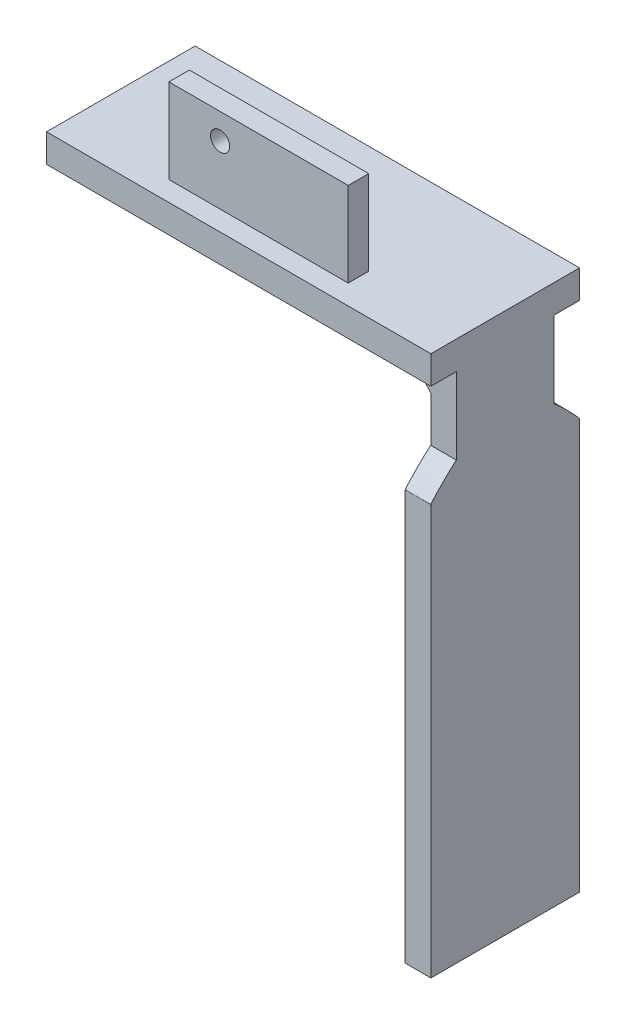
SolidWorks part; units mm, degrees
ref_plane "Front Plane" through (0, 0, 0) normal (0, 0, 1) x (1, 0, 0)
ref_plane "Top Plane" through (0, 0, 0) normal (0, 1, 0) x (1, 0, 0)
ref_plane "Right Plane" through (0, 0, 0) normal (1, 0, 0) x (0, 0, -1)
sketch "Sketch1" plane through (0, 0, 0) normal (0, 1, 0) x (1, 0, 0)
  line L1 (0, 0) -> (60, 0)
  line L2 (0, 0) -> (0, -23.2)
  line L3 (0, -23.2) -> (60, -23.2)
  line L4 (60, 0) -> (60, -23.2)
  dimension "D1" = 23.2
  dimension "D2" = 60
extrude "Boss-Extrude1" add sketch "Sketch1" along normal blind 4.4
sketch "Sketch2" plane through (0, 4.4, 0) normal (0, 1, 0) x (1, 0, 0)
  line L0 (0, -23.2) -> (60, -23.2) construction
  line L1 (16, -16.9) -> (44, -16.9)
  line L2 (16, -16.9) -> (16, -20.1)
  line L3 (16, -20.1) -> (44, -20.1)
  line L4 (44, -16.9) -> (44, -20.1)
  point P7 (30, -23.2)
  point P8 (30, -20.1)
  dimension "D1" = 3.1
  dimension "D2" = 3.2
  dimension "D3" = 28
extrude "Boss-Extrude2" add sketch "Sketch2" along normal blind 13.2
sketch "Sketch3" plane through (0, 0, 0) normal (0, -1, 0) x (-1, 0, 0)
  line L0 (-60, -23.2) -> (-60, 0) construction
  line L1 (-60, -4) -> (-56, -4)
  line L2 (-60, -4) -> (-60, -19.2)
  line L3 (-60, -19.2) -> (-56, -19.2)
  line L4 (-56, -4) -> (-56, -19.2)
  line L5 (-60, 0) -> (0, 0) construction
  point P6 (-60, -11.6)
  dimension "D2" = 11.6
  dimension "D3" = 15.2
extrude "Boss-Extrude3" add sketch "Sketch3" along normal blind 80
sketch "Sketch4" plane through (56, 0, 0) normal (-1, 0, 0) x (0, 0, 1)
  line L1 (19.2, -80) -> (23.2, -80)
  line L2 (19.2, -80) -> (19.2, -12)
  line L3 (19.2, -12) -> (23.2, -12)
  line L4 (23.2, -80) -> (23.2, -12)
  line L5 (4, -80) -> (0, -80)
  line L6 (4, -80) -> (4, -12)
  line L7 (4, -12) -> (0, -12)
  line L8 (0, -80) -> (0, -12)
  dimension "D2" = 4
  dimension "D3" = 68
  dimension "D4" = 68
extrude "Boss-Extrude4" add sketch "Sketch4" against normal blind 4
fillet "Fillet1" radius 5 1 edges at (56, 0, 11.6) conic rho 0.05
fillet "Fillet2" radius 4 2 edges at (58, -12, 0) (58, -12, 23.2) conic rho 0.05
sketch "Sketch5" plane through (0, 0, 20.1) normal (0, 0, 1) x (1, 0, 0)
  line L0 (16, 17.6) -> (44, 17.6) construction
  line L1 (16, 17.6) -> (16, 4.4) construction
  circle A0 centre (24, 13.6) radius 1.5
  dimension "D2" = 4
  dimension "D3" = 8
extrude "Cut-Extrude1" cut sketch "Sketch5" against normal blind 10
equation "\"滑动-垂直孔\" = 0.6"
equation "\"滑动-水平孔\" = 0.3"
equation "\"松动-垂直孔\" = 0.3"
equation "\"松动-水平孔\" = 0.1"
equation "\"正常-垂直孔\" = 0.15"
equation "\"正常-水平孔\" = 0"
equation "\"紧缩-垂直孔\" = 0"
equation "\"紧缩-水平孔\" = -0.1"
equation "\"_喷嘴物理宽度\" = 0.8"
equation "\"_喷嘴宽度系数\" = 1"
equation "\"_物理厚度\" = 0.4"
equation "\"_物理厚度系数\" = 2"
equation "\"喷嘴宽度\" = \"_喷嘴物理宽度\" * \"_喷嘴宽度系数\""
equation "\"喷嘴厚度\" = \"_物理厚度\" * \"_物理厚度系数\""
equation "\"D1@Sketch1\"=\"喷嘴宽度\"*29"
equation "\"D2@Sketch1\"=\"喷嘴宽度\"*200/2 - \"喷嘴宽度\"*50/2"
equation "\"D1@Boss-Extrude1\"=\"喷嘴厚度\"*5.5"
equation "\"D2@Sketch2\"=\"喷嘴宽度\"*4"
equation "\"D3@Sketch2\"=\"喷嘴宽度\"*35"
equation "\"D1@Boss-Extrude2\"=\"喷嘴厚度\"*16.5"
equation "\"D1@Sketch3\"=\"喷嘴宽度\"*5"
equation "\"D2@Sketch3\"=\"D1@Sketch1\"/2"
equation "\"D3@Sketch3\"=\"喷嘴宽度\"*19"
equation "\"D1@Sketch4\"=\"喷嘴宽度\"*5"
equation "\"D2@Sketch4\"=\"D1@Sketch4\""
equation "\"D3@Sketch4\"=\"喷嘴宽度\"*85"
equation "\"D4@Sketch4\"=\"D3@Sketch4\""
equation "\"D1@Boss-Extrude4\"=\"喷嘴宽度\"*5"
equation "\"D1@Sketch5\"=\"正常-水平孔\"+3"
equation "\"D2@Sketch5\"=\"喷嘴厚度\"*5"
equation "\"D3@Sketch5\"=\"喷嘴厚度\"*10"
